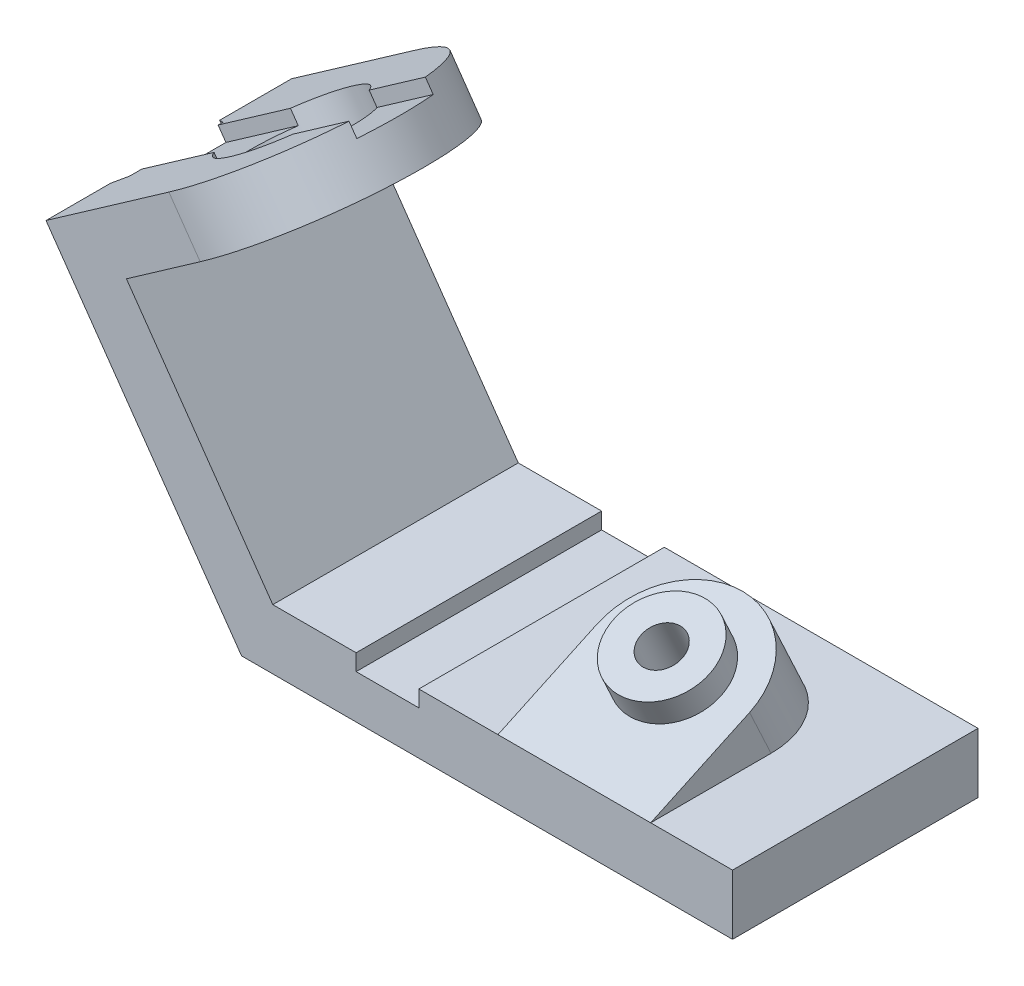
SolidWorks part; units mm, degrees
material "1060 Alloy"
ref_plane "Front Plane" through (0, 0, 0) normal (0, 0, 1) x (1, 0, 0)
ref_plane "Top Plane" through (0, 0, 0) normal (0, 1, 0) x (1, 0, 0)
ref_plane "Right Plane" through (0, 0, 0) normal (1, 0, 0) x (0, 0, -1)
sketch "Sketch1" plane through (0, 0, 0) normal (0, 1, 0) x (1, 0, 0)
  line L0 (0, 0) -> (0, 58861.3153) construction
  line L1 (0, 0) -> (58861.3153, 0) construction
  line L3 (-90, 45) -> (90, 45)
  line L4 (-90, 45) -> (-90, -45)
  line L5 (-90, -45) -> (90, -45)
  line L6 (90, 45) -> (90, -45)
  dimension "D1" = 180
  dimension "D2" = 90
extrude "Boss-Extrude1" add sketch "Sketch1" along normal blind 22
sketch "Sketch2" plane through (0, 22, 0) normal (0, 1, 0) x (1, 0, 0)
  line L0 (90, 45) -> (-90, 45) construction
  line L1 (-48, 45) -> (-25, 45)
  line L2 (-48, 45) -> (-48, -45)
  line L3 (-48, -45) -> (-25, -45)
  line L4 (-25, 45) -> (-25, -45)
  line L5 (-90, -45) -> (90, -45) construction
  line L6 (90, -45) -> (90, 45) construction
  dimension "D1" = 23
  dimension "D2" = 115
extrude "Cut-Extrude1" cut sketch "Sketch2" against normal blind 6
ref_plane "Plane1" through (0, 35.3067, 16.4638) normal (0, 0.9063, 0.4226) x (1, 0, 0)
sketch "Sketch3" plane through (0, 35.3067, 16.4638) normal (0, 0.9063, 0.4226) x (1, 0, 0)
  line L0 (4, -31.4862) -> (4, 8.5138)
  line L1 (-25, -31.4862) -> (90, -31.4862) construction
  line L2 (60, 8.5138) -> (60, -31.4862)
  line L3 (60, -31.4862) -> (4, -31.4862)
  arc A0 (4, 8.5138) -> (60, 8.5138) centre (32, 8.5138) cw
  point P6 (62.858, 16.8299)
  point P8 (0, 0)
  dimension "D1" = 30
  dimension "D2" = 56
  dimension "D3" = 40
extrude "Boss-Extrude2" add sketch "Sketch3" against normal up to surface up to face at (32.5, 22, 0)
ref_plane "Plane2" through (0, 44.3697, 20.69) normal (0, 0.9063, 0.4226) x (1, 0, 0)
sketch "Sketch4" plane through (0, 44.3697, 20.69) normal (0, 0.9063, 0.4226) x (1, 0, 0)
  circle A0 centre (32, 8.5138) radius 17.5
  circle A1 centre (32, 8.5138) radius 7.5
  dimension "D1" = 35
  dimension "D2" = 15
extrude "Boss-Extrude3" add sketch "Sketch4" against normal up to surface (10 mm away) up to face at (32, 33.4107, 20.5297)
sketch "Sketch5" plane through (0, 35.3067, 16.4638) normal (0, 0.9063, 0.4226) x (1, 0, 0)
  circle A0 centre (32, 8.5138) radius 7.5 construction
  circle A1 centre (32, 8.5138) radius 7.5
extrude "Cut-Extrude2" cut sketch "Sketch5" against normal through all
ref_plane "Plane3" through (-60.3909, -42.2862, 0) normal (-0.8192, -0.5736, 0) x (0, 0, 1)
sketch "Sketch6" plane through (-60.3909, -42.2862, 0) normal (-0.8192, -0.5736, 0) x (0, 0, 1)
  line L0 (-45, 51.6219) -> (-45, 176.6219)
  line L1 (-45, 176.6219) -> (45, 176.6219)
  line L2 (45, 176.6219) -> (45, 51.6219)
  line L3 (45, 51.6219) -> (-45, 51.6219)
  dimension "D1" = 125
extrude "Boss-Extrude4" add sketch "Sketch6" against normal blind 22
sketch "Sketch8" plane through (-101.3061, 144.6802, 0) normal (-0.5736, 0.8192, 0) x (0.8192, 0.5736, 0)
  line L0 (-73.7237, 18.6621) -> (-68.7237, 15.7754)
  line L1 (-73.7237, -45) -> (-73.7237, 45) construction
  line L2 (-68.7237, 15.7754) -> (-68.7237, -18.4511)
  line L3 (-68.7237, -18.4511) -> (-73.7237, -21.3379)
  line L4 (-73.7237, -21.3379) -> (-73.7237, 18.6621)
  line L5 (-73.7237, 18.6621) -> (-53.5519, 18.6621) construction
  dimension "D1" = 40
  dimension "D3" = 5
  dimension "D4" = 30
extrude "Cut-Extrude3" cut sketch "Sketch8" against normal through all
ref_plane "Plane4" through (-101.3061, 144.6802, 0) normal (-0.5736, 0.8192, 0) x (0, 0, -1)
sketch "Sketch9" plane through (-101.3061, 144.6802, 0) normal (-0.5736, 0.8192, 0) x (0, 0, -1)
  line L0 (45, 73.7237) -> (45, 18.7237)
  line L1 (-45, 18.7237) -> (-45, 73.7237)
  line L2 (-45, 73.7237) -> (-21.3379, 73.7237) construction
  line L3 (-21.3379, 73.7237) -> (-18.4511, 68.7237) construction
  line L4 (15.7754, 68.7237) -> (18.6621, 73.7237) construction
  line L5 (-18.4511, 68.7237) -> (15.7754, 68.7237) construction
  line L6 (18.6621, 73.7237) -> (45, 73.7237) construction
  line L7 (-45, 73.7237) -> (-21.3379, 73.7237)
  line L8 (-21.3379, 73.7237) -> (-18.4511, 68.7237)
  line L9 (15.7754, 68.7237) -> (18.6621, 73.7237)
  line L10 (-18.4511, 68.7237) -> (15.7754, 68.7237)
  line L11 (18.6621, 73.7237) -> (45, 73.7237)
  arc A0 (45, 18.7237) -> (-45, 18.7237) centre (0, 18.7237) cw
  circle A1 centre (0, 18.7237) radius 22.5
  circle A2 centre (0, 18.7237) radius 11
  dimension "D2" = 45
  dimension "D3" = 22
  dimension "D1" = 55
extrude "Boss-Extrude5" add sketch "Sketch9" against normal blind 20 contours A0 L0 L11 L9 L10 L8 L7 L1 A1 region at (-139.1704, 118.1674, -43.6546)
extrude "Boss-Extrude6" add sketch "Sketch9<3>" against normal up to surface (20 mm away) from offset 12 contours A1 A2 region at (-116.6437, 133.9407, 21.8636) up to face at (-109.4727, 114.5464, 0) offset against normal yes
sketch "Sketch9<3>" plane through (-101.3061, 144.6802, 0) normal (-0.5736, 0.8192, 0) x (0, 0, -1) same geometry as "Sketch9"
sketch "Sketch11" plane through (-101.3061, 144.6802, 0) normal (-0.5736, 0.8192, 0) x (0.8192, 0.5736, 0)
  line L0 (-68.7237, 14) -> (24.0431, 14)
  line L1 (-68.7237, -18.4511) -> (-68.7237, 15.7754) construction
  line L2 (-68.7237, -14) -> (24.0431, -14)
  line L3 (-68.7237, -14) -> (-68.7237, 14)
  line L4 (-18.7237, 0) -> (-98.4467, 0) construction
  arc A0 (-18.7237, -45) -> (-18.7237, 45) centre (-18.7237, 0) ccw construction
  circle A1 centre (-18.7237, 0) radius 22.5 construction
  arc A2 (-36.3376, 14) -> (-36.3376, -14) centre (-18.7237, 0) ccw
  arc A3 (24.0431, -14) -> (24.0431, 14) centre (-18.7237, 0) ccw
  arc A4 (-1.1098, -14) -> (-1.1098, 14) centre (-18.7237, 0) ccw
  line M7 (-68.7237, 15.7754) -> (-68.7237, -18.4511)
  arc M11 (-18.7237, -45) -> (-18.7237, 45) centre (-18.7237, 0) ccw
  circle M14 centre (-18.7237, 0) radius 22.5
  dimension "D1" = 28
extrude "Cut-Extrude4" cut sketch "Sketch11" against normal blind 5 contours L4 A2 L0 M7 | L4 L3 L2 M14 | L2 L0 M14 M11 region at (-145.674, 113.6134, -7.1911) region at (-145.674, 113.6134, 7.1911) region at (-89.9624, 152.6232, 0)
equation "\"A\"= 180"
